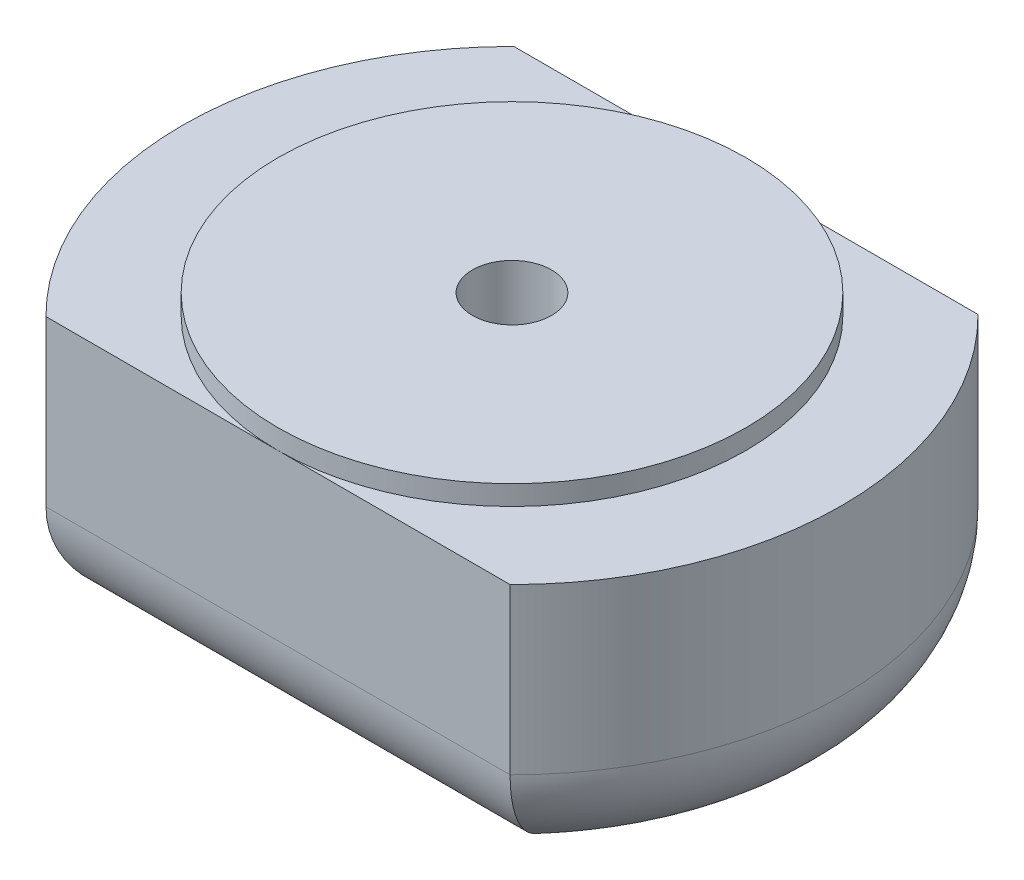
SolidWorks part; units mm, degrees
ref_plane "前视基准面" through (0, 0, 0) normal (0, 0, 1) x (1, 0, 0)
ref_plane "上视基准面" through (0, 0, 0) normal (0, 1, 0) x (1, 0, 0)
ref_plane "右视基准面" through (0, 0, 0) normal (1, 0, 0) x (0, 0, -1)
other "Configuration Table"
sketch "草图1" plane through (0, 0, 0) normal (0, 1, 0) x (1, 0, 0)
  circle A0 centre (0, 0) radius 5
  dimension "D1" = 10
extrude "凸台-拉伸1" add sketch "草图1" along normal blind 4
sketch "草图2" plane through (0, 4, 0) normal (0, 1, 0) x (1, 0, 0)
  circle A0 centre (0, 0) radius 3.55
  dimension "D1" = 7.1
extrude "凸台-拉伸2" add sketch "草图2" along normal blind 0.3
sketch "草图3" plane through (0, 4.3, 0) normal (0, 1, 0) x (1, 0, 0)
  circle A0 centre (0, 0) radius 0.6
  dimension "D1" = 1.2
extrude "切除-拉伸1" cut sketch "草图3" against normal through all
sketch "草图4" plane through (0, 4, 0) normal (0, 1, 0) x (1, 0, 0)
  line L1 (-5, 3.55) -> (5, 3.55)
  line L2 (-5, 3.55) -> (-5, -3.55)
  line L3 (-5, -3.55) -> (5, -3.55)
  line L4 (5, 3.55) -> (5, -3.55)
  line L5 (-5, 3.55) -> (5, -3.55) construction
  line L6 (-5, -3.55) -> (5, 3.55) construction
  circle A0 centre (0, 0) radius 3.55 construction
  circle A1 centre (0, 0) radius 5 construction
  point P0 (0, 0)
extrude "切除-拉伸2" cut sketch "草图4" against normal through all flip side to cut
fillet "圆角1" radius 1.5 4 edges at (5, 0, 0) (0, 0, -3.55) (-5, 0, 0) (0, 0, 3.55)
